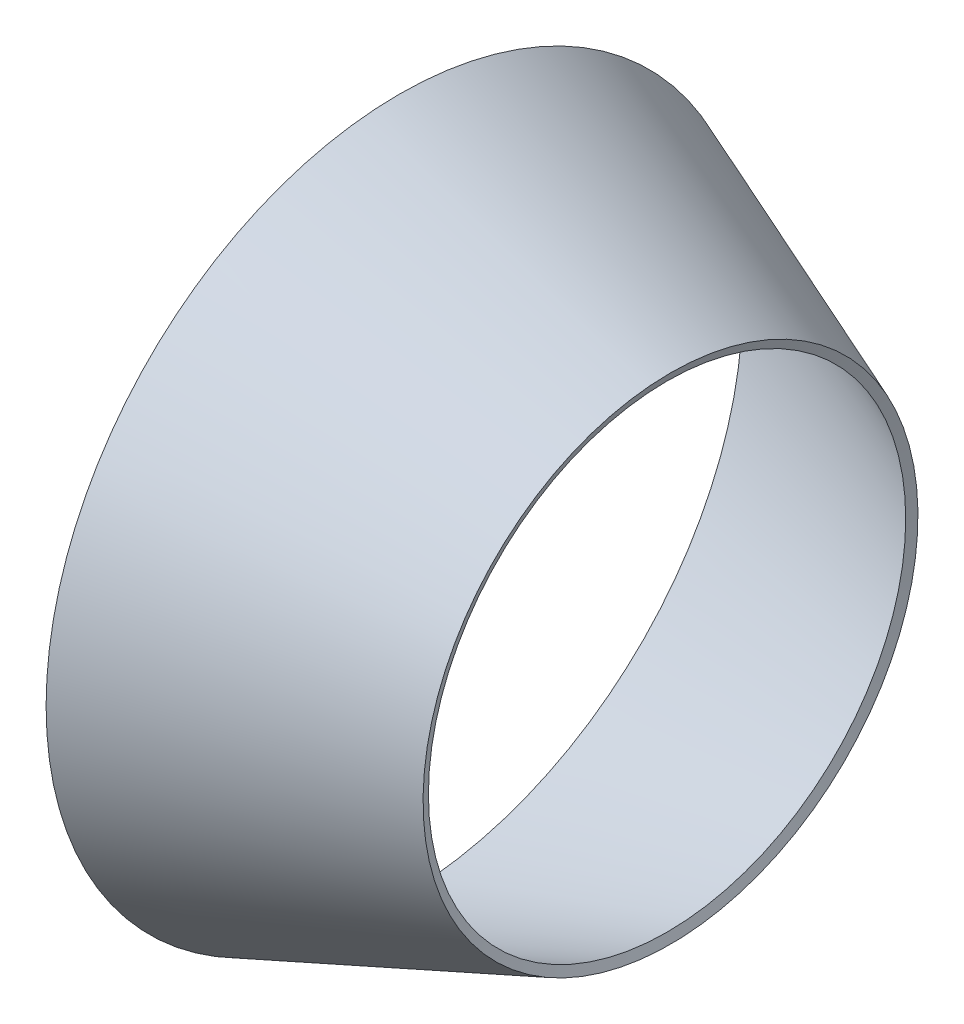
SolidWorks part; units mm, degrees
ref_plane "Front Plane" through (0, 0, 0) normal (0, 0, 1) x (1, 0, 0)
ref_plane "Top Plane" through (0, 0, 0) normal (0, 1, 0) x (1, 0, 0)
ref_plane "Right Plane" through (0, 0, 0) normal (1, 0, 0) x (0, 0, -1)
sketch "Sketch1" plane through (0, 0, 0) normal (0, 0, 1) x (1, 0, 0)
  line L0 (-42.0913, -47.5161) -> (-5.626, -33.2811)
  line L1 (-42.0913, -47.5161) -> (-42.0913, 47.5161) construction
  line L2 (-5.626, -33.2811) -> (-6.0878, -32.098)
  line L3 (-6.0878, -32.098) -> (-42.0913, -46.1527)
  line L4 (-42.0913, -45.72) -> (-42.0913, 45.72) construction
  line L5 (0, 0) -> (-88.1772, 0) construction
  line L6 (-129.4673, 0) -> (-46.8871, 0) construction
  line L7 (-42.0913, -47.5161) -> (-42.0913, -46.1527)
  point P6 (-42.0913, -47.4185)
  point P9 (-42.0913, -45.7268)
  point P10 (-42.0913, -47.5161)
  point P16 (-8.3834, -29.7391)
  point P17 (-6.69, -31.8559)
  point P18 (-6.0878, -33.2811)
  dimension "D1" = 1.27
revolve "Revolve1" add sketch "Sketch1" angle 360 about L5
